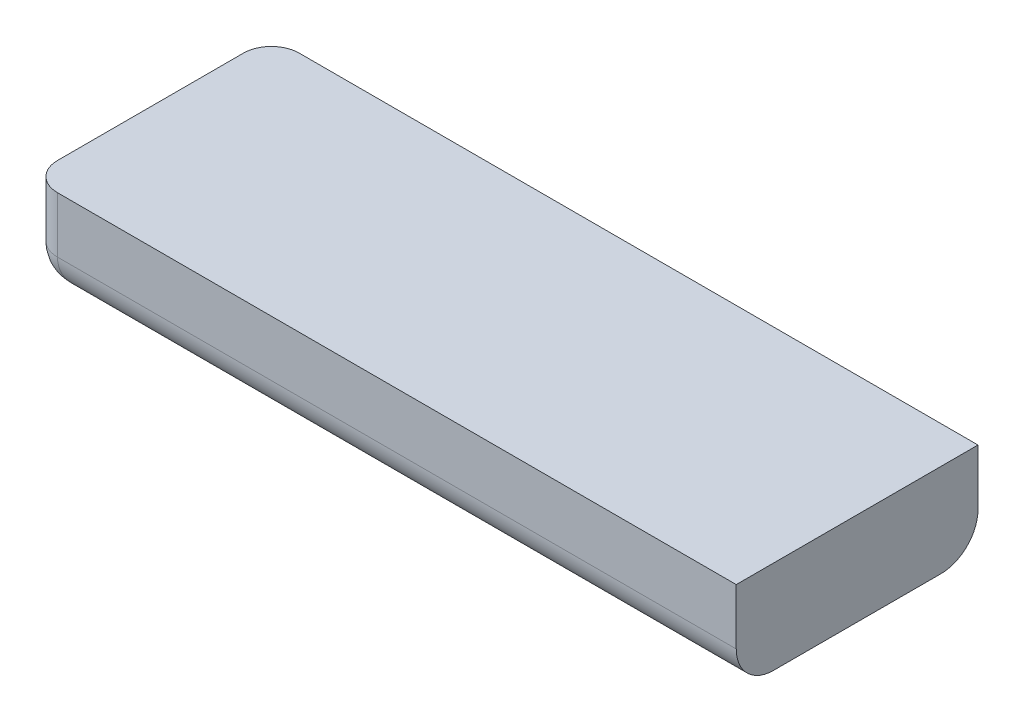
SolidWorks part; units mm, degrees
ref_plane "Piano frontale" through (0, 0, 0) normal (0, 0, 1) x (1, 0, 0)
ref_plane "Piano superiore" through (0, 0, 0) normal (0, 1, 0) x (1, 0, 0)
ref_plane "Piano destro" through (0, 0, 0) normal (1, 0, 0) x (0, 0, -1)
sketch "Schizzo1" plane through (0, 0, 0) normal (0, 0, 1) x (1, 0, 0)
  line L0 (-48, 0) -> (83.1953, 0) construction
  line L2 (-48, 0) -> (-10, 0)
  line L3 (-48, 0) -> (-48, 5)
  line L4 (-48, 5) -> (-10, 5)
  line L5 (-10, 0) -> (-10, 5)
  dimension "D1" = 10
  dimension "D2" = 5
  dimension "D3" = 38
extrude "Estrusione-Estrusione1" add sketch "Schizzo1" along normal blind 13
fillet "Raccordo1" radius 1.5 2 edges at (-48, 2.5, 13) (-48, 2.5, 0)
fillet "Raccordo2" radius 2 5 edges at (-48, 0, 6.5) (-28.25, 0, 13) (-47.5607, 0, 12.5607) (-28.25, 0, 0) (-47.5607, 0, 0.4393)
